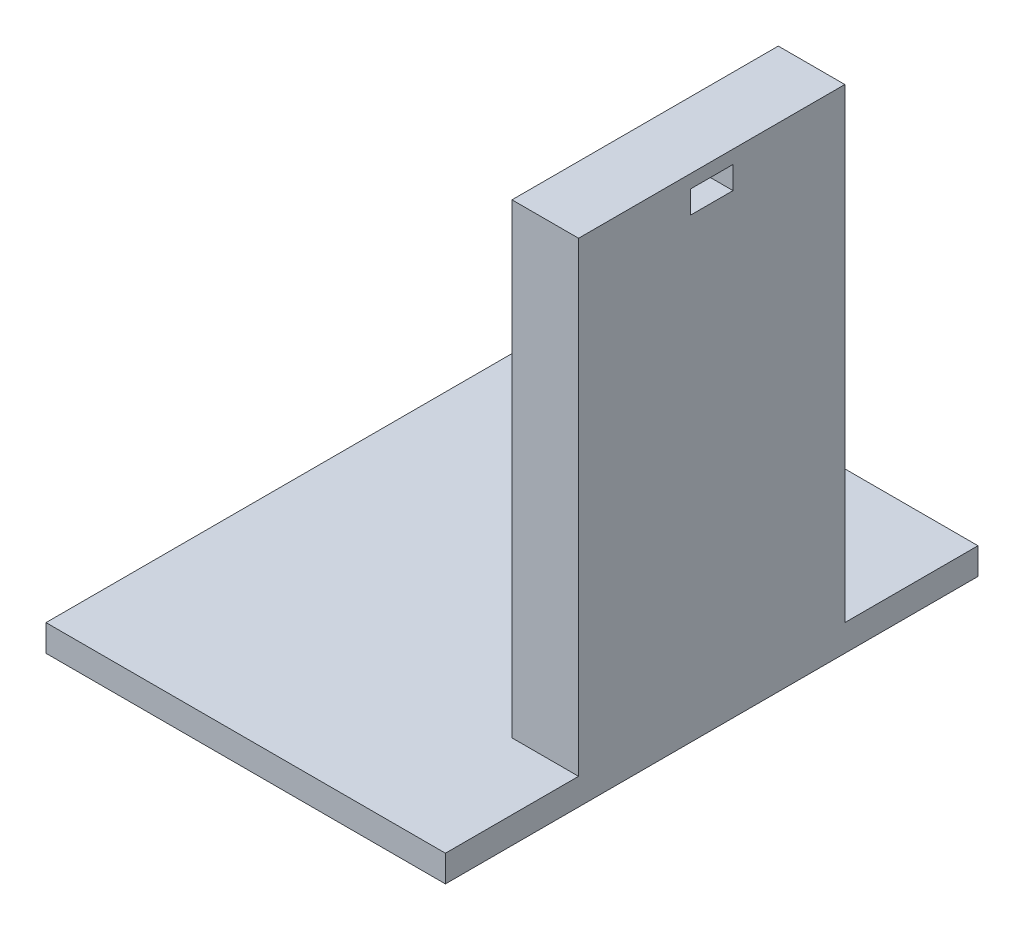
SolidWorks part; units mm, degrees
ref_plane "Plan de face" through (0, 0, 0) normal (0, 0, 1) x (1, 0, 0)
ref_plane "Plan de dessus" through (0, 0, 0) normal (0, 1, 0) x (1, 0, 0)
ref_plane "Plan de droite" through (0, 0, 0) normal (1, 0, 0) x (0, 0, -1)
sketch "Esquisse2" plane through (0, 0, 0) normal (0, 1, 0) x (1, 0, 0)
  line L0 (54.6919, 181.7) -> (54.6919, -18.3)
  line L1 (-95.3081, 181.7) -> (54.6919, 181.7)
  line L2 (-95.3081, 181.7) -> (-95.3081, -18.3)
  line L3 (-95.3081, -18.3) -> (54.6919, -18.3)
extrude "Boss.-Extru.6" add sketch "Esquisse2" along normal blind 10
sketch "Esquisse4" plane through (0, 0, 0) normal (0, 1, 0) x (1, 0, 0)
  line L0 (29.6919, 31.7) -> (54.6919, 31.7)
  line L1 (29.6919, 31.7) -> (29.6919, 131.7)
  line L2 (29.6919, 131.7) -> (54.6919, 131.7)
  line L3 (54.6919, 31.7) -> (54.6919, 131.7)
  line L4 (54.6919, -18.3) -> (54.6919, 181.7) construction
  line L5 (54.6919, -18.3) -> (54.6919, 181.7)
extrude "Boss.-Extru.7" add sketch "Esquisse4" along normal blind 180 contours L0 L3 L2 L1 region at (42.1919, 0, -81.7)
sketch "Esquisse8" plane through (29.6919, 0, 0) normal (-1, 0, 0) x (0, 0, 1)
  line L0 (-93.9, 159.9717) -> (-69.5, 159.9717)
  line L1 (-93.9, 159.9717) -> (-93.9, 180)
  line L2 (-93.9, 180) -> (-69.5, 180)
  line L3 (-69.5, 159.9717) -> (-69.5, 180)
  line L4 (-31.7, 180) -> (-131.7, 180) construction
  point P6 (-81.7, 180)
  dimension "D1" = 20.0283
  dimension "D2" = 24.4
extrude "Enlèv. mat.-Extru.1" cut sketch "Esquisse8" against normal blind 12.2
sketch "Esquisse9" plane through (41.8919, 0, 0) normal (-1, 0, 0) x (0, 0, 1)
  line L0 (-87.7, 178.4859) -> (-87.7, 173.4859) construction
  line L1 (-87.7, 173.4859) -> (-75.7, 173.4859) construction
  line L2 (-75.7, 173.4859) -> (-75.7, 178.4859) construction
  line L3 (-75.7, 178.4859) -> (-87.7, 178.4859) construction
  line L4 (-81.7, 180) -> (-81.7, 178.4859) construction
  line L6 (-69.5, 180) -> (-93.9, 180) construction
  line L7 (-87.7, 178.4859) -> (-87.7, 173.4859)
  line L8 (-87.7, 173.4859) -> (-75.7, 173.4859)
  line L9 (-75.7, 173.4859) -> (-75.7, 178.4859)
  line L10 (-75.7, 178.4859) -> (-87.7, 178.4859)
  point P6 (-81.7, 178.4859)
  dimension "D1" = 1.5141
  dimension "D2" = 5
  dimension "D3" = 12
extrude "Enlèv. mat.-Extru.2" cut sketch "Esquisse9" against normal blind 42.2
sketch "Esquisse11" plane through (41.8919, 0, 0) normal (-1, 0, 0) x (0, 0, 1)
  line L0 (-69.5, 180) -> (-93.9, 180) construction
  line L1 (-89.7, 180) -> (-73.7, 180)
  line L2 (-89.7, 180) -> (-89.7, 171.4859)
  line L3 (-89.7, 171.4859) -> (-73.7, 171.4859)
  line L4 (-73.7, 180) -> (-73.7, 171.4859)
  line L5 (-87.7, 175.7429) -> (-89.7, 175.7429) construction
  line L6 (-87.7, 178.4859) -> (-87.7, 173.4859) construction
  line L7 (-75.7, 175.9859) -> (-73.7, 175.9859) construction
  line L8 (-75.7, 173.4859) -> (-75.7, 178.4859) construction
  line L9 (-81.7, 173.4859) -> (-81.7, 171.4859) construction
  line L10 (-87.7, 173.4859) -> (-75.7, 173.4859) construction
  dimension "D1" = 2
  dimension "D2" = 2
  dimension "D3" = 2
extrude "Enlèv. mat.-Extru.3" cut sketch "Esquisse11" against normal blind 42.2
sketch "Esquisse12" plane through (29.6919, 0, 0) normal (-1, 0, 0) x (0, 0, 1)
  line L0 (-94.4, 180) -> (-94.4, 159.97)
  line L1 (-93.9, 180) -> (-131.7, 180) construction
  line L3 (-69, 159.97) -> (-69, 180)
  line L4 (-31.7, 180) -> (-69.5, 180) construction
  line L5 (-69, 180) -> (-69.5, 180)
  line L6 (-69.5, 180) -> (-69.5, 159.9717)
  line L8 (-93.9, 159.9717) -> (-93.9, 180)
  line L9 (-93.9, 180) -> (-94.4, 180)
  line L10 (-79.5159, 139.9717) -> (-79.5159, 139.4717) construction
  line L11 (-69, 159.97) -> (-69.5, 159.9717)
  line L13 (-93.9, 159.9717) -> (-94.4, 159.97)
  dimension "D1" = 0.5
  dimension "D2" = 0.5
  dimension "D3" = 20.0283
  dimension "D4" = 20.03
  dimension "D5" = 20.03
extrude "Enlèv. mat.-Extru.6" cut sketch "Esquisse12" against normal blind 12.2
sketch "Esquisse13" plane through (0, 180, 0) normal (0, 1, 0) x (1, 0, 0)
  line L1 (29.6919, 131.7) -> (54.6919, 131.7)
  line L2 (29.6919, 131.7) -> (29.6919, 31.7)
  line L3 (29.6919, 31.7) -> (54.6919, 31.7)
  line L4 (54.6919, 131.7) -> (54.6919, 31.7)
extrude "Boss.-Extru.8" add sketch "Esquisse13" along normal blind 5
sketch "Esquisse14" plane through (29.6919, 0, 0) normal (-1, 0, 0) x (0, 0, 1)
  line L0 (-94.4, 180) -> (-94.4, 180.5)
  line L2 (-94.4, 180) -> (-69, 180)
  line L4 (-69, 180) -> (-69, 180.5)
  line L5 (-69, 180.5) -> (-94.4, 180.5)
  dimension "D1" = 0.5
extrude "Enlèv. mat.-Extru.7" cut sketch "Esquisse14" against normal blind 12.2
sketch "Esquisse15" plane through (54.6919, 0, 0) normal (1, 0, 0) x (0, 0, -1)
  line L0 (-18.3, 0) -> (181.7, 0) construction
  line L1 (31.7, 185) -> (131.7, 185) construction
  line L2 (-18.3, 0) -> (181.7, 0)
  line L3 (31.7, 185) -> (131.7, 185)
  dimension "D1" = 185
